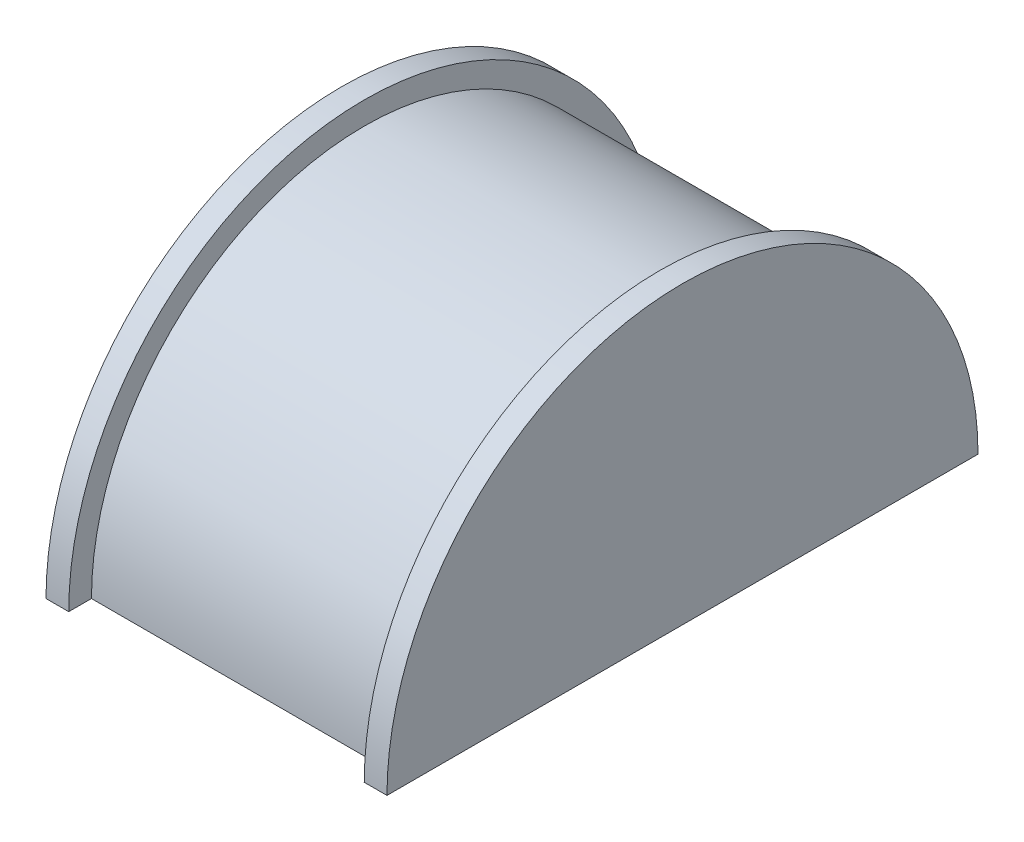
SolidWorks part; units mm, degrees
ref_plane "Front Plane" through (0, 0, 0) normal (0, 0, 1) x (1, 0, 0)
ref_plane "Top Plane" through (0, 0, 0) normal (0, 1, 0) x (1, 0, 0)
ref_plane "Right Plane" through (0, 0, 0) normal (1, 0, 0) x (0, 0, -1)
sketch "Sketch2" plane through (0, 0, 0) normal (1, 0, 0) x (0, 0, -1)
  line L0 (-6, 0) -> (6, 0)
  arc A0 (6, 0) -> (-6, 0) centre (0, 0) ccw
  dimension "D1" = 12
extrude "Boss-Extrude1" add sketch "Sketch2" along normal blind 6.5
ref_plane "Plane1" through (3.25, 0, 0) normal (1, 0, 0) x (0, 0, -1)
sketch "Sketch3" plane through (6.5, 0, 0) normal (1, 0, 0) x (0, 0, -1)
  line L0 (-6, 0) -> (6, 0) construction
  line L1 (-6.5, 0) -> (6.5, 0)
  arc A0 (6.5, 0) -> (-6.5, 0) centre (0, 0) ccw
  arc A1 (6, 0) -> (-6, 0) centre (0, 0) ccw construction
  dimension "D1" = 0.5
extrude "Boss-Extrude2" add sketch "Sketch3" along normal blind 0.5
mirror "Mirror1" about plane through (3.25, 0, 0) normal (1, 0, 0) of "Boss-Extrude2"
sketch "Sketch4" plane through (0, 0, 0) normal (0, -1, 0) x (1, 0, 0)
  line L0 (3.25, -6) -> (3.25, 6) construction
  line L1 (6.5, -6) -> (0, -6) construction
  line L2 (6.5, 6) -> (0, 6) construction
  circle A0 centre (3.25, 0) radius 1.75
  dimension "D1" = 3.5
extrude "Cut-Extrude1" cut sketch "Sketch4" against normal blind 5
equation "\"X-ROD-SPACING\"=45"
equation "\"Y-ROD-SPACING\"=75"
equation "\"Z-ROD-SPACING\"=17.5"
equation "\"Y-BED-OFFSET\"=2"
equation "\"Y-BED-ROD-INSET\"=3.5"
equation "\"Y-BED-SCREW-SPACING\"=209"
equation "\"Y-BED-SCREW-CUTOUT-SLOT-HEIGHT\"=2.5"
equation "\"T-SLOT-NUT-FILLET-RADIUS\"=0.5"
equation "\"T-SLOT-SCREW-SHAFT-RADIUS\"=1.55"
equation "\"T-SLOT-SCREW-SHAFT-CUTOUT-LENGTH\"=11"
equation "\"T-SLOT-NUT-DEPTH\"=3.5"
equation "\"T-SLOT-NUT-WIDTH\"=2.85"
equation "\"T-SLOT-NUT-END-DISTANCE\"=8"
equation "\"ACRYLIC-THICKNESS\"=10"
equation "\"ACRYLIC-THICKNESS2\"=4.5"
equation "\"ACRYLIC-TAB-CUTOUT-SIZE\"=\"ACRYLIC-THICKNESS\"+\"ACRYLIC-TAB-TOLERANCE\"*2"
equation "\"ACRYLIC-TAB-TOLERANCE\"=-.05"
equation "\"KERF\"=0.075"
equation "\"ACRYLIC-THICKNESS-TAB-CUTOUT-WIDTH\"=\"ACRYLIC-THICKNESS\"-\"KERF\"*2"
equation "\"ACRYLIC-THICKNESS-TAB-CUTOUT-HEIGHT\"=\"ACRYLIC-TAB-WIDTH\"-\"KERF\"*4"
equation "\"ACRYLIC-THICKNESS2-TAB-CUTOUT-WIDTH\"=\"ACRYLIC-THICKNESS2\"-\"KERF\"*2"
equation "\"ACRYLIC-THICKNESS2-TAB-CUTOUT-HEIGHT\"=\"ACRYLIC-TAB-WIDTH\"-\"KERF\"*4"
equation "\"ACRYLIC-TAB-WIDTH\"=\"ACRYLIC-THICKNESS\""
equation "\"ACRYLIC-M3-HOLE\"=2.9"
equation "\"SMOOTHROD-CAP-SCREW-DISTANCE\"=20"
equation "\"FRAME-WIDTH-INNER\"=370"
equation "\"NEMA17-HOLE-SPACING\"=31"
equation "\"NEMA17-CENTRAL-CUTOUT\"=22.5"
equation "\"Z-BRACKET-REACH\"=57"
equation "\"Z-ROD-INSET\"=13.5"
equation "\"TOP-BRACKET-SPACING\"=40"
equation "\"SMOOTHROD-X-LENGTH\"=350"
equation "\"SMOOTHROD-Y-LENGTH\"=350"
equation "\"SMOOTHROD-Z-LENGTH\"=350"
equation "\"SMOOTHROD-TIGHTENING-HEADROOM\"=.25"
equation "\"LEADSCREW-Z-LENGTH\"=300"
equation "\"SCREW-LENGTH-FRAME\"=\"ACRYLIC-THICKNESS\" + 10"
equation "\"SCREW-LENGTH-MOTOR\"=\"ACRYLIC-THICKNESS\" + 5"
equation "\"SCREW-LENGTH-EXTRUDER\"=28"
equation "\"SCREW-HEAD-RADIUS\"=6"
equation "\"PRINTED-M3-HOLE\"=3.5"
equation "\"PRINTED-X-SMOOTHROD-DIAMETER\"=8.8"
equation "\"PRINTED-X-SMOOTHROD-CUTOUT\"=10"
equation "\"PRINTED-X-BASE-HEIGHT\"=10"
equation "\"PRINTED-LM8UU-CUTOUT-SIZE\"=15.5"
equation "\"PRINTED-LM8UU-CUTOUT-LENGTH\"=24.5"
equation "\"PRINTED-X-IDLER-HEIGHT\"=16"
equation "\"PRINTED-M3-NUT-AF\"=6.25"
equation "\"PSU-MOUNTING-WIDTH\"=95"
equation "\"PSU-MOUNTING-HEIGHT\"=177"
equation "\"Y-BELT-TO-ROD-DISTANCE\"=20"
equation "\"SPOOL-HOLDER-ROD-SPACING\"=150"
equation "\"ACRYLIC-X-CARRIAGE-WIDTH\"=55"
equation "\"ACRYLIC-X-CARRIAGE-HEIGHT\"=75"
equation "\"ACRYLIC-X-CARRIAGE-LM8UU-CUTOUT-WIDTH\"=24.25"
equation "\"ACRYLIC-X-CARRIAGE-LM8UU-CUTOUT-HEIGHT\"=11.0"
equation "\"ACRYLIC-X-CARRIAGE-SCREW-SPACING-X\"=15"
equation "\"ACRYLIC-X-CARRIAGE-SCREW-SPACING-Y\"=33"
equation "\"ACRYLIC-X-CARRIAGE-CENTER-TAB-SPACING\"=14"
equation "\"ACRYLIC-X-CARRIAGE-EXTRUDER-OFFSET\"=26"
equation "\"ACRYLIC-X-CARRIAGE-EXTRUDER-ANGLE\"=90"
equation "\"ACRYLIC-X-CARRIAGE-EXTRUDER-SHELF-DEPTH\"=\"ACRYLIC-X-CARRIAGE-EXTRUDER-OFFSET\" + 28"
equation "\"ACRYLIC-X-CARRIAGE-EXTRUDER-BRACE-SPACING\"=23"
equation "\"ACRYLIC-X-CARRIAGE-EXTRUDER-BRACE-TAB-OFFSET\"=20"
equation "\"ACRYLIC-X-CARRIAGE-EXTRUDER-BRACE-HEIGHT\"=35"
equation "\"ACRYLIC-X-CARRIAGE-EXTRUDER-BRACE-SCREW-SPACING\"=22"
equation "\"ACRYLIC-X-CARRIAGE-DUAL-WIDTH-MULTIPLIER\"=1.65"
equation "\"ACRYLIC-X-CARRIAGE-DUAL-HOTEND-SPACING\"=42"
equation "\"ACRYLIC-X-CARRIAGE-DUAL-WIDTH\"=75"
equation "\"ACRYLIC-X-CARRIAGE-DUAL-FAN-OFFSET\"=52"
equation "\"ACRYLIC-X-CARRIAGE-DUAL-FAN-HEIGHT\"=20"
equation "\"ACRYLIC-X-CARRIAGE-DUAL-HOTEND-SEPARATION\"=36"
equation "\"ACRYLIC-X-CARRIAGE-DUAL-MOUNT-PLATE-DEPTH\"=75"
equation "\"ACRYLIC-X-CARRIAGE-DUAL-MOUNT-BRACE-WIDTH\"=33"
equation "\"ACRYLIC-X-CARRIAGE-DUAL-MOUNT-SCREW-WIDTH\"=40"
equation "\"BLOWER-FAN-WIDTH\"=15"
